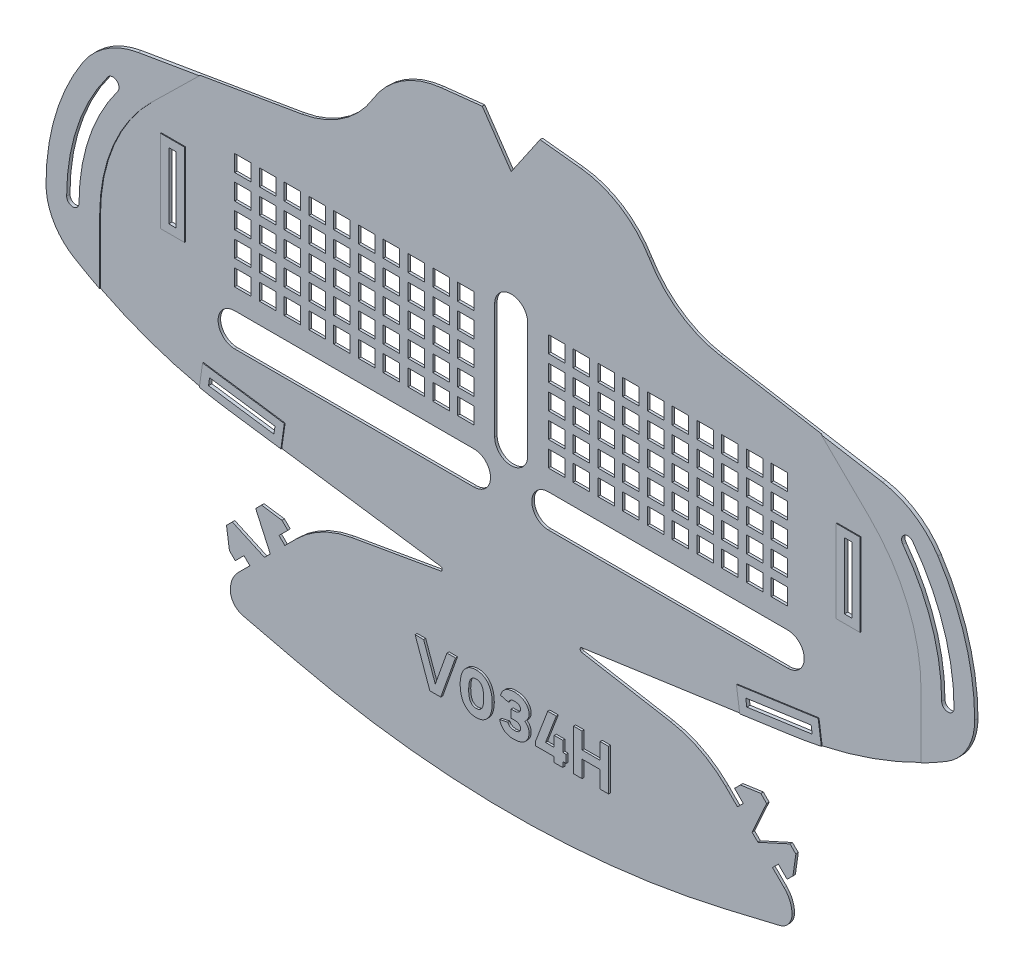
SolidWorks part; units mm, degrees
ref_plane "Front Plane" through (0, 0, 0) normal (0, 0, 1) x (1, 0, 0)
ref_plane "Top Plane" through (0, 0, 0) normal (0, 1, 0) x (1, 0, 0)
ref_plane "Right Plane" through (0, 0, 0) normal (1, 0, 0) x (0, 0, -1)
sketch "Sketch1" plane through (0, 0, 0) normal (0, 0, 1) x (1, 0, 0)
  line L0 (0, 0) -> (0, -145) construction
  line L1 (-14, -102) -> (14, -102) construction
  line L2 (-112.5, -69) -> (112.5, -69) construction
  line L3 (0, -10.2352) -> (-7, 0)
  line L4 (0, -10.2352) -> (7, 0)
  line L5 (7, 0) -> (16.9419, -1.0768)
  line L6 (-90.1804, -30.1909) -> (-50.7439, -23.5)
  line L7 (90.1804, -30.1909) -> (50.7439, -23.5)
  line L8 (-14, -102) -> (-68.2662, -94.2919)
  line L9 (-7, 0) -> (-16.9419, -1.0768)
  line L10 (14, -102) -> (68.2662, -94.2919)
  line L11 (-103.5977, -39) -> (-103.5977, -69) construction
  line L12 (-14, -102) -> (-38.6266, -106.305)
  line L13 (-52, -113.2546) -> (-54.8283, -116.0832)
  line L14 (52, -113.2546) -> (54.8283, -116.0832)
  line L15 (14, -102) -> (38.6266, -106.305)
  line L16 (-54.8283, -116.0832) -> (-56.2426, -114.669)
  line L17 (-56.2426, -114.669) -> (-54.1214, -112.5476)
  line L18 (-54.1214, -112.5476) -> (-55.5356, -111.1334)
  line L19 (-55.5356, -111.1334) -> (-60.4854, -110.4265)
  line L20 (-60.4854, -110.4265) -> (-68.9703, -118.9122)
  line L21 (-64.7275, -123.1546) -> (-63.3132, -124.5688)
  line L22 (-63.3132, -124.5688) -> (-66.1415, -127.3973)
  line L23 (-64.7275, -123.1546) -> (-66.8487, -125.2761)
  line L24 (-66.8487, -125.2761) -> (-68.263, -123.8619)
  line L25 (-68.9703, -118.9122) -> (-68.263, -123.8619)
  line L26 (68.9703, -118.9122) -> (68.263, -123.8619)
  line L27 (66.8487, -125.2761) -> (68.263, -123.8619)
  line L28 (64.7275, -123.1546) -> (66.8487, -125.2761)
  line L29 (63.3132, -124.5688) -> (66.1415, -127.3973)
  line L30 (64.7275, -123.1546) -> (63.3132, -124.5688)
  line L31 (60.4854, -110.4265) -> (68.9703, -118.9122)
  line L32 (55.5356, -111.1334) -> (60.4854, -110.4265)
  line L33 (54.1214, -112.5476) -> (55.5356, -111.1334)
  line L34 (56.2426, -114.669) -> (54.1214, -112.5476)
  line L35 (54.8283, -116.0832) -> (56.2426, -114.669)
  line L36 (-64.9691, -135.8852) -> (-52.4361, -138.8607)
  line L37 (64.9691, -135.8852) -> (52.4361, -138.8607)
  line L38 (-68.9703, -118.9122) -> (-64.7275, -123.1546) construction
  line L39 (-60.4854, -110.4265) -> (-56.2426, -114.669) construction
  arc A0 (-16.9419, -1.0768) -> (-33.4614, -11.6696) centre (-14.5729, -22.9489) ccw
  arc A1 (-33.4614, -11.6696) -> (-50.7439, -23.5) centre (-54.9257, 1.1478) cw
  arc A2 (-103.5977, -39) -> (-90.1804, -30.1909) centre (-86.8349, -49.9091) cw
  arc A3 (-112.5, -69) -> (-103.5977, -39) centre (-57.5, -69) cw
  arc A4 (112.5, -69) -> (103.5977, -39) centre (57.5, -69) ccw
  arc A5 (103.5977, -39) -> (90.1804, -30.1909) centre (86.8349, -49.9091) ccw
  arc A6 (16.9419, -1.0768) -> (33.4614, -11.6696) centre (14.5729, -22.9489) cw
  arc A7 (33.4614, -11.6696) -> (50.7439, -23.5) centre (54.9257, 1.1478) ccw
  arc A8 (-112.5, -69) -> (-105.7111, -81) centre (-98.5, -69) ccw
  arc A9 (-105.7111, -81) -> (-68.2662, -94.2919) centre (-54.2032, 4.7143) ccw
  arc A10 (112.5, -69) -> (105.7111, -81) centre (98.5, -69) cw
  arc A11 (105.7111, -81) -> (68.2662, -94.2919) centre (54.2032, 4.7143) cw
  arc A12 (-38.6266, -106.305) -> (-52, -113.2546) centre (-34.3216, -130.9315) ccw
  arc A13 (38.6266, -106.305) -> (52, -113.2546) centre (34.3216, -130.9315) cw
  arc A14 (-66.1415, -127.3973) -> (-68.0451, -131.9933) centre (-61.5451, -131.9933) ccw
  arc A15 (-68.0451, -131.9933) -> (-64.9691, -135.8852) centre (-64.0451, -131.9933) ccw
  arc A16 (68.0451, -131.9933) -> (64.9691, -135.8852) centre (64.0451, -131.9933) cw
  arc A17 (66.1415, -127.3973) -> (68.0451, -131.9933) centre (61.5451, -131.9933) cw
  arc A19 (-52.4361, -138.8607) -> (0, -145) centre (0, 82) ccw
  arc A20 (52.4361, -138.8607) -> (0, -145) centre (0, 82) cw
  point P8 (0, -102)
  point P11 (0, -69)
  dimension "D5" = 55
  dimension "D11" = 20
  dimension "D13" = 25
  dimension "D16" = 14
  dimension "D15" = 22
  dimension "D18" = 100
  dimension "D22" = 25
  dimension "D31" = 6.5
  dimension "D32" = 4
  dimension "D34" = 227
  dimension "D1" = 145
  dimension "D2" = 28
  dimension "D3" = 43
  dimension "D4" = 76
  dimension "D6" = 225
  dimension "D7" = 14
  dimension "D8" = 12.4
  dimension "D9" = 10
  dimension "D10" = 30
  dimension "D12" = 40
  dimension "D14" = 45.5
  dimension "D17" = 12
  dimension "D19" = 18
  dimension "D20" = 25
  dimension "D21" = 4
  dimension "D23" = 38
  dimension "D24" = 2
  dimension "D25" = 3
  dimension "D26" = 2
  dimension "D27" = 18
  dimension "D29" = 8
  dimension "D30" = 4
extrude "Main Shape" add sketch "Sketch1" along normal blind 0.6
sketch "Sketch2" plane through (0, 0, 0.6) normal (0, 0, 1) x (1, 0, 0)
  line L0 (0, -55) -> (0, 55) construction
  arc A0 (-96.3, -39.9) -> (-106, -69) centre (-57.5, -69) ccw construction
  arc A1 (-97.5, -39) -> (-107.5, -69) centre (-57.5, -69) ccw
  arc A2 (-95.1, -40.8) -> (-104.5, -69) centre (-57.5, -69) ccw
  arc A3 (-95.1, -40.8) -> (-97.5, -39) centre (-96.3, -39.9) ccw
  arc A4 (-107.5, -69) -> (-104.5, -69) centre (-106, -69) ccw
  arc A6 (-103.5977, -39) -> (-112.5, -69) centre (-57.5, -69) ccw construction
  arc A7 (96.3, -39.9) -> (106, -69) centre (57.5, -69) cw construction
  arc A8 (97.5, -39) -> (107.5, -69) centre (57.5, -69) cw
  arc A9 (95.1, -40.8) -> (104.5, -69) centre (57.5, -69) cw
  arc A10 (95.1, -40.8) -> (97.5, -39) centre (96.3, -39.9) cw
  arc A11 (107.5, -69) -> (104.5, -69) centre (106, -69) cw
  point P3 (-103.5111, -53.663)
  point P19 (103.5111, -53.663)
  dimension "D1" = 5
  dimension "D2" = 1.5
extrude "Elastic Attachment Points" cut sketch "Sketch2" against normal through all
sketch "Sketch7" plane through (0, 0, 0.6) normal (0, 0, 1) x (1, 0, 0)
  line L0 (-99.5, -69) -> (-99.5, -84.4384)
  line L1 (-86.8939, -39) -> (-75.3319, -27.6717)
  line L2 (-50.7439, -23.5) -> (-90.1804, -30.1909) construction
  line L3 (-75.3319, -27.6717) -> (-90.1804, -30.1909)
  line L4 (0, -55) -> (0, 55) construction
  line L5 (75.3319, -27.6717) -> (90.1804, -30.1909)
  line L6 (86.8939, -39) -> (75.3319, -27.6717)
  line L7 (99.5, -69) -> (99.5, -84.4384)
  arc A0 (-99.5, -69) -> (-86.8939, -39) centre (-57.5, -69) cw
  arc A1 (-95.1, -40.8) -> (-104.5, -69) centre (-57.5, -69) ccw construction
  arc A2 (-105.7111, -81) -> (-68.2662, -94.2919) centre (-54.2032, 4.7143) ccw construction
  arc A3 (-112.5, -69) -> (-105.7111, -81) centre (-98.5, -69) ccw construction
  arc A4 (-103.5977, -39) -> (-112.5, -69) centre (-57.5, -69) ccw construction
  arc A5 (-90.1804, -30.1909) -> (-103.5977, -39) centre (-86.8349, -49.9091) ccw construction
  arc A6 (-105.7111, -81) -> (-99.5, -84.4384) centre (-54.2032, 4.7143) ccw
  arc A7 (-112.5, -69) -> (-105.7111, -81) centre (-98.5, -69) ccw
  arc A8 (-103.5977, -39) -> (-112.5, -69) centre (-57.5, -69) ccw
  arc A9 (-90.1804, -30.1909) -> (-103.5977, -39) centre (-86.8349, -49.9091) ccw
  arc A10 (90.1804, -30.1909) -> (103.5977, -39) centre (86.8349, -49.9091) cw
  arc A11 (103.5977, -39) -> (112.5, -69) centre (57.5, -69) cw
  arc A12 (112.5, -69) -> (105.7111, -81) centre (98.5, -69) cw
  arc A13 (105.7111, -81) -> (99.5, -84.4384) centre (54.2032, 4.7143) cw
  arc A14 (99.5, -69) -> (86.8939, -39) centre (57.5, -69) ccw
  arc A15 (-107.5, -69) -> (-104.5, -69) centre (-106, -69) ccw construction
  arc A16 (-95.1, -40.8) -> (-97.5, -39) centre (-96.3, -39.9) ccw construction
  arc A17 (-97.5, -39) -> (-107.5, -69) centre (-57.5, -69) ccw construction
  arc A18 (-107.5, -69) -> (-104.5, -69) centre (-106, -69) ccw
  arc A19 (-95.1, -40.8) -> (-97.5, -39) centre (-96.3, -39.9) ccw
  arc A20 (-95.1, -40.8) -> (-104.5, -69) centre (-57.5, -69) ccw
  arc A21 (-97.5, -39) -> (-107.5, -69) centre (-57.5, -69) ccw
  arc A22 (104.5, -69) -> (107.5, -69) centre (106, -69) ccw construction
  arc A23 (97.5, -39) -> (95.1, -40.8) centre (96.3, -39.9) ccw construction
  arc A24 (104.5, -69) -> (95.1, -40.8) centre (57.5, -69) ccw construction
  arc A25 (107.5, -69) -> (97.5, -39) centre (57.5, -69) ccw construction
  arc A26 (104.5, -69) -> (107.5, -69) centre (106, -69) ccw
  arc A27 (97.5, -39) -> (95.1, -40.8) centre (96.3, -39.9) ccw
  arc A28 (104.5, -69) -> (95.1, -40.8) centre (57.5, -69) ccw
  arc A29 (107.5, -69) -> (97.5, -39) centre (57.5, -69) ccw
  dimension "D1" = 5
extrude "Reinforced Attachment Points" add sketch "Sketch7" along normal blind 0.2
sketch "Sketch6" plane through (0, 0, 0.6) normal (0, 0, 1) x (1, 0, 0)
  line L0 (-73.1225, -91.5821) -> (-57.2815, -93.8322)
  line L1 (-57.2815, -93.8322) -> (-57.0283, -92.05)
  line L2 (-57.0283, -92.05) -> (-72.8693, -89.8)
  line L3 (-72.8693, -89.8) -> (-73.1225, -91.5821)
  line L4 (-68.2662, -94.2919) -> (-14, -102) construction
  line L5 (-64.9488, -90.925) -> (-65.202, -92.7071) construction
  line L13 (0, -0.44) -> (0, 0.44) construction
  line L14 (64.9488, -90.925) -> (65.202, -92.7071) construction
  line L15 (73.1225, -91.5821) -> (72.8693, -89.8)
  line L16 (57.0283, -92.05) -> (57.2815, -93.8322)
  line L22 (57.0283, -92.05) -> (72.8693, -89.8)
  line L24 (73.1225, -91.5821) -> (57.2815, -93.8322)
  dimension "D1" = 2
  dimension "D2" = 16
  dimension "D3" = 52
  dimension "D4" = 1.8
extrude "Tab Slits" cut sketch "Sketch6" against normal through all
sketch "Sketch9" plane through (0, 0, 0.6) normal (0, 0, 1) x (1, 0, 0)
  line L4 (-57.2815, -93.8322) -> (-57.0283, -92.05) construction
  line L5 (-73.1225, -91.5821) -> (-57.2815, -93.8322) construction
  line L6 (-72.8693, -89.8) -> (-73.1225, -91.5821) construction
  line L7 (-57.0283, -92.05) -> (-72.8693, -89.8) construction
  line L12 (-57.2815, -93.8322) -> (-57.0283, -92.05)
  line L13 (-73.1225, -91.5821) -> (-57.2815, -93.8322)
  line L14 (-72.8693, -89.8) -> (-73.1225, -91.5821)
  line L15 (-57.0283, -92.05) -> (-72.8693, -89.8)
  line L16 (-55.5826, -96.0935) -> (-54.767, -90.3512)
  line L17 (-68.2662, -94.2919) -> (-14, -102) construction
  line L18 (-54.767, -90.3512) -> (-74.5682, -87.5386)
  line L19 (-74.5682, -87.5386) -> (-75.3475, -93.0248)
  line L20 (-68.2662, -94.2919) -> (-55.5826, -96.0935)
  line L21 (0, -0.44) -> (0, 0.44) construction
  line L22 (68.2662, -94.2919) -> (55.5826, -96.0935)
  line L23 (74.5682, -87.5386) -> (75.3475, -93.0248)
  line L24 (54.767, -90.3512) -> (74.5682, -87.5386)
  line L25 (55.5826, -96.0935) -> (54.767, -90.3512)
  line L26 (57.0283, -92.05) -> (72.8693, -89.8)
  line L27 (72.8693, -89.8) -> (73.1225, -91.5821)
  line L28 (73.1225, -91.5821) -> (57.2815, -93.8322)
  line L29 (57.2815, -93.8322) -> (57.0283, -92.05)
  arc A0 (-99.5, -84.4384) -> (-68.2662, -94.2919) centre (-54.2032, 4.7143) ccw construction
  arc A1 (-75.3475, -93.0248) -> (-68.2662, -94.2919) centre (-54.2032, 4.7143) ccw
  arc A2 (75.3475, -93.0248) -> (68.2662, -94.2919) centre (54.2032, 4.7143) cw
  dimension "D1" = 2
  dimension "D2" = 2
  dimension "D3" = 2
extrude "Reinforced Tab Slits" add sketch "Sketch9" along normal blind 0.2
sketch "Sketch11" plane through (0, 0, 0.6) normal (0, 0, 1) x (1, 0, 0)
  line L0 (-67.5562, -117.4979) -> (-59.7778, -121.0331)
  line L1 (-60.4854, -110.4265) -> (-68.9703, -118.9122) construction
  line L2 (-59.7778, -121.0331) -> (-58.3637, -119.6188)
  line L3 (-58.3637, -119.6188) -> (-61.8996, -111.8408)
  line L4 (-61.8996, -111.8408) -> (-67.5562, -117.4979)
  line L6 (-58.3637, -119.6188) -> (-54.8283, -116.0832) construction
  line L7 (-59.7778, -121.0331) -> (-63.3132, -124.5688) construction
  line L10 (0, -0.44) -> (0, 0.44) construction
  line L11 (59.7778, -121.0331) -> (63.3132, -124.5688) construction
  line L12 (58.3637, -119.6188) -> (54.8283, -116.0832) construction
  line L13 (61.8996, -111.8408) -> (67.5562, -117.4979)
  line L14 (58.3637, -119.6188) -> (61.8996, -111.8408)
  line L15 (59.7778, -121.0331) -> (58.3637, -119.6188)
  line L16 (67.5562, -117.4979) -> (59.7778, -121.0331)
  dimension "D1" = 2
  dimension "D2" = 2
  dimension "D3" = 5
extrude "Tab Flex Relief" cut sketch "Sketch11" against normal through all both and the other way through all
sketch "Sketch3" plane through (0, 0, 0.6) normal (0, 0, 1) x (1, 0, 0)
  line L3 (0, -10.2352) -> (0, -145) construction
  line L4 (-106, -69) -> (-96.3, -69) construction
  line L5 (-96.3, -69) -> (-96.3, -39.9) construction
  line L6 (-13, -39.9) -> (-9, -39.9)
  line L9 (-13, -39.9) -> (-13, -43.9)
  line L12 (-13, -43.9) -> (-9, -43.9)
  line L15 (-9, -39.9) -> (-9, -43.9)
  line L427 (0, -39.9) -> (0, -67.9) construction
  line L428 (4, -39.9) -> (4, -67.9)
  line L429 (-4, -39.9) -> (-4, -67.9)
  line L430 (-19, -39.9) -> (-15, -39.9)
  line L431 (-19, -39.9) -> (-19, -43.9)
  line L432 (-19, -43.9) -> (-15, -43.9)
  line L433 (-15, -39.9) -> (-15, -43.9)
  line L434 (-25, -39.9) -> (-21, -39.9)
  line L435 (-25, -39.9) -> (-25, -43.9)
  line L436 (-25, -43.9) -> (-21, -43.9)
  line L437 (-21, -39.9) -> (-21, -43.9)
  line L438 (-31, -39.9) -> (-27, -39.9)
  line L439 (-31, -39.9) -> (-31, -43.9)
  line L440 (-31, -43.9) -> (-27, -43.9)
  line L441 (-27, -39.9) -> (-27, -43.9)
  line L442 (-37, -39.9) -> (-33, -39.9)
  line L443 (-37, -39.9) -> (-37, -43.9)
  line L444 (-67, -76.9) -> (-9, -76.9) construction
  line L445 (-67, -72.9) -> (-9, -72.9)
  line L446 (-67, -80.9) -> (-9, -80.9)
  line L447 (67, -76.9) -> (9, -76.9) construction
  line L448 (67, -72.9) -> (9, -72.9)
  line L449 (67, -80.9) -> (9, -80.9)
  line L452 (-37, -43.9) -> (-33, -43.9)
  line L453 (-33, -39.9) -> (-33, -43.9)
  line L454 (-43, -39.9) -> (-39, -39.9)
  line L457 (-43, -39.9) -> (-43, -43.9)
  line L458 (-43, -43.9) -> (-39, -43.9)
  line L459 (-39, -39.9) -> (-39, -43.9)
  line L460 (-49, -39.9) -> (-45, -39.9)
  line L461 (-49, -39.9) -> (-49, -43.9)
  line L462 (-49, -43.9) -> (-45, -43.9)
  line L463 (-45, -39.9) -> (-45, -43.9)
  line L464 (-55, -39.9) -> (-51, -39.9)
  line L465 (-55, -39.9) -> (-55, -43.9)
  line L466 (-55, -43.9) -> (-51, -43.9)
  line L467 (-51, -39.9) -> (-51, -43.9)
  line L468 (-61, -39.9) -> (-57, -39.9)
  line L469 (-61, -39.9) -> (-61, -43.9)
  line L470 (-61, -43.9) -> (-57, -43.9)
  line L471 (-57, -39.9) -> (-57, -43.9)
  line L472 (-67, -39.9) -> (-63, -39.9)
  line L473 (-67, -39.9) -> (-67, -43.9)
  line L474 (-67, -43.9) -> (-63, -43.9)
  line L475 (-63, -39.9) -> (-63, -43.9)
  line L476 (-19, -45.9) -> (-15, -45.9)
  line L477 (-19, -45.9) -> (-19, -49.9)
  line L478 (-19, -49.9) -> (-15, -49.9)
  line L479 (-15, -45.9) -> (-15, -49.9)
  line L480 (-25, -45.9) -> (-21, -45.9)
  line L481 (-25, -45.9) -> (-25, -49.9)
  line L482 (-25, -49.9) -> (-21, -49.9)
  line L483 (-21, -45.9) -> (-21, -49.9)
  line L484 (-31, -45.9) -> (-27, -45.9)
  line L485 (-31, -45.9) -> (-31, -49.9)
  line L486 (-31, -49.9) -> (-27, -49.9)
  line L487 (-27, -45.9) -> (-27, -49.9)
  line L488 (-37, -45.9) -> (-33, -45.9)
  line L489 (-37, -45.9) -> (-37, -49.9)
  line L490 (-37, -49.9) -> (-33, -49.9)
  line L491 (-33, -45.9) -> (-33, -49.9)
  line L492 (-43, -45.9) -> (-39, -45.9)
  line L493 (-43, -45.9) -> (-43, -49.9)
  line L494 (-43, -49.9) -> (-39, -49.9)
  line L495 (-39, -45.9) -> (-39, -49.9)
  line L496 (-49, -45.9) -> (-45, -45.9)
  line L497 (-49, -45.9) -> (-49, -49.9)
  line L498 (-49, -49.9) -> (-45, -49.9)
  line L499 (-45, -45.9) -> (-45, -49.9)
  line L500 (-55, -45.9) -> (-51, -45.9)
  line L501 (-55, -45.9) -> (-55, -49.9)
  line L502 (-55, -49.9) -> (-51, -49.9)
  line L503 (-51, -45.9) -> (-51, -49.9)
  line L504 (-61, -45.9) -> (-57, -45.9)
  line L505 (-61, -45.9) -> (-61, -49.9)
  line L506 (-61, -49.9) -> (-57, -49.9)
  line L507 (-57, -45.9) -> (-57, -49.9)
  line L508 (-67, -45.9) -> (-63, -45.9)
  line L509 (-67, -45.9) -> (-67, -49.9)
  line L510 (-67, -49.9) -> (-63, -49.9)
  line L511 (-63, -45.9) -> (-63, -49.9)
  line L512 (-19, -51.9) -> (-15, -51.9)
  line L513 (-19, -51.9) -> (-19, -55.9)
  line L514 (-19, -55.9) -> (-15, -55.9)
  line L515 (-15, -51.9) -> (-15, -55.9)
  line L516 (-25, -51.9) -> (-21, -51.9)
  line L517 (-25, -51.9) -> (-25, -55.9)
  line L518 (-25, -55.9) -> (-21, -55.9)
  line L519 (-21, -51.9) -> (-21, -55.9)
  line L520 (-31, -51.9) -> (-27, -51.9)
  line L521 (-31, -51.9) -> (-31, -55.9)
  line L522 (-31, -55.9) -> (-27, -55.9)
  line L523 (-27, -51.9) -> (-27, -55.9)
  line L524 (-37, -51.9) -> (-33, -51.9)
  line L525 (-37, -51.9) -> (-37, -55.9)
  line L526 (-37, -55.9) -> (-33, -55.9)
  line L527 (-33, -51.9) -> (-33, -55.9)
  line L528 (-43, -51.9) -> (-39, -51.9)
  line L529 (-43, -51.9) -> (-43, -55.9)
  line L530 (-43, -55.9) -> (-39, -55.9)
  line L531 (-39, -51.9) -> (-39, -55.9)
  line L532 (-49, -51.9) -> (-45, -51.9)
  line L533 (-49, -51.9) -> (-49, -55.9)
  line L534 (-49, -55.9) -> (-45, -55.9)
  line L535 (-45, -51.9) -> (-45, -55.9)
  line L536 (-55, -51.9) -> (-51, -51.9)
  line L537 (-55, -51.9) -> (-55, -55.9)
  line L538 (-55, -55.9) -> (-51, -55.9)
  line L539 (-51, -51.9) -> (-51, -55.9)
  line L540 (-61, -51.9) -> (-57, -51.9)
  line L541 (-61, -51.9) -> (-61, -55.9)
  line L542 (-61, -55.9) -> (-57, -55.9)
  line L543 (-57, -51.9) -> (-57, -55.9)
  line L544 (-67, -51.9) -> (-63, -51.9)
  line L545 (-67, -51.9) -> (-67, -55.9)
  line L546 (-67, -55.9) -> (-63, -55.9)
  line L547 (-63, -51.9) -> (-63, -55.9)
  line L548 (-19, -57.9) -> (-15, -57.9)
  line L549 (-19, -57.9) -> (-19, -61.9)
  line L550 (-19, -61.9) -> (-15, -61.9)
  line L551 (-15, -57.9) -> (-15, -61.9)
  line L552 (-25, -57.9) -> (-21, -57.9)
  line L553 (-25, -57.9) -> (-25, -61.9)
  line L554 (-25, -61.9) -> (-21, -61.9)
  line L555 (-21, -57.9) -> (-21, -61.9)
  line L556 (-31, -57.9) -> (-27, -57.9)
  line L557 (-31, -57.9) -> (-31, -61.9)
  line L558 (-31, -61.9) -> (-27, -61.9)
  line L559 (-27, -57.9) -> (-27, -61.9)
  line L560 (-37, -57.9) -> (-33, -57.9)
  line L561 (-37, -57.9) -> (-37, -61.9)
  line L562 (-37, -61.9) -> (-33, -61.9)
  line L563 (-33, -57.9) -> (-33, -61.9)
  line L564 (-43, -57.9) -> (-39, -57.9)
  line L565 (-43, -57.9) -> (-43, -61.9)
  line L566 (-43, -61.9) -> (-39, -61.9)
  line L567 (-39, -57.9) -> (-39, -61.9)
  line L568 (-49, -57.9) -> (-45, -57.9)
  line L569 (-49, -57.9) -> (-49, -61.9)
  line L570 (-49, -61.9) -> (-45, -61.9)
  line L571 (-45, -57.9) -> (-45, -61.9)
  line L572 (-55, -57.9) -> (-51, -57.9)
  line L573 (-55, -57.9) -> (-55, -61.9)
  line L574 (-55, -61.9) -> (-51, -61.9)
  line L575 (-51, -57.9) -> (-51, -61.9)
  line L576 (-61, -57.9) -> (-57, -57.9)
  line L577 (-61, -57.9) -> (-61, -61.9)
  line L578 (-61, -61.9) -> (-57, -61.9)
  line L579 (-57, -57.9) -> (-57, -61.9)
  line L580 (-67, -57.9) -> (-63, -57.9)
  line L581 (-67, -57.9) -> (-67, -61.9)
  line L582 (-67, -61.9) -> (-63, -61.9)
  line L583 (-63, -57.9) -> (-63, -61.9)
  line L584 (-19, -63.9) -> (-15, -63.9)
  line L585 (-19, -63.9) -> (-19, -67.9)
  line L586 (-19, -67.9) -> (-15, -67.9)
  line L587 (-15, -63.9) -> (-15, -67.9)
  line L588 (-25, -63.9) -> (-21, -63.9)
  line L589 (-25, -63.9) -> (-25, -67.9)
  line L590 (-25, -67.9) -> (-21, -67.9)
  line L591 (-21, -63.9) -> (-21, -67.9)
  line L592 (-31, -63.9) -> (-27, -63.9)
  line L593 (-31, -63.9) -> (-31, -67.9)
  line L594 (-31, -67.9) -> (-27, -67.9)
  line L595 (-27, -63.9) -> (-27, -67.9)
  line L596 (-37, -63.9) -> (-33, -63.9)
  line L597 (-37, -63.9) -> (-37, -67.9)
  line L598 (-37, -67.9) -> (-33, -67.9)
  line L599 (-33, -63.9) -> (-33, -67.9)
  line L600 (-43, -63.9) -> (-39, -63.9)
  line L601 (-43, -63.9) -> (-43, -67.9)
  line L602 (-43, -67.9) -> (-39, -67.9)
  line L603 (-39, -63.9) -> (-39, -67.9)
  line L604 (-49, -63.9) -> (-45, -63.9)
  line L605 (-49, -63.9) -> (-49, -67.9)
  line L606 (-49, -67.9) -> (-45, -67.9)
  line L607 (-45, -63.9) -> (-45, -67.9)
  line L608 (-55, -63.9) -> (-51, -63.9)
  line L609 (-55, -63.9) -> (-55, -67.9)
  line L610 (-55, -67.9) -> (-51, -67.9)
  line L611 (-51, -63.9) -> (-51, -67.9)
  line L612 (-61, -63.9) -> (-57, -63.9)
  line L613 (-61, -63.9) -> (-61, -67.9)
  line L614 (-61, -67.9) -> (-57, -67.9)
  line L615 (-57, -63.9) -> (-57, -67.9)
  line L616 (-67, -63.9) -> (-63, -63.9)
  line L617 (-67, -63.9) -> (-67, -67.9)
  line L618 (-67, -67.9) -> (-63, -67.9)
  line L619 (-63, -63.9) -> (-63, -67.9)
  line L620 (-13, -45.9) -> (-9, -45.9)
  line L621 (-13, -45.9) -> (-13, -49.9)
  line L622 (-13, -49.9) -> (-9, -49.9)
  line L623 (-9, -45.9) -> (-9, -49.9)
  line L624 (-13, -51.9) -> (-9, -51.9)
  line L625 (-13, -51.9) -> (-13, -55.9)
  line L626 (-13, -55.9) -> (-9, -55.9)
  line L627 (-9, -51.9) -> (-9, -55.9)
  line L628 (-13, -57.9) -> (-9, -57.9)
  line L629 (-13, -57.9) -> (-13, -61.9)
  line L630 (-13, -61.9) -> (-9, -61.9)
  line L631 (-9, -57.9) -> (-9, -61.9)
  line L632 (-13, -63.9) -> (-9, -63.9)
  line L633 (-13, -63.9) -> (-13, -67.9)
  line L634 (-13, -67.9) -> (-9, -67.9)
  line L635 (-9, -63.9) -> (-9, -67.9)
  line L636 (9, -63.9) -> (9, -67.9)
  line L637 (13, -67.9) -> (9, -67.9)
  line L638 (13, -63.9) -> (13, -67.9)
  line L639 (13, -63.9) -> (9, -63.9)
  line L640 (9, -57.9) -> (9, -61.9)
  line L641 (13, -61.9) -> (9, -61.9)
  line L642 (13, -57.9) -> (13, -61.9)
  line L643 (13, -57.9) -> (9, -57.9)
  line L644 (9, -51.9) -> (9, -55.9)
  line L645 (13, -55.9) -> (9, -55.9)
  line L646 (13, -51.9) -> (13, -55.9)
  line L647 (13, -51.9) -> (9, -51.9)
  line L648 (9, -45.9) -> (9, -49.9)
  line L649 (13, -49.9) -> (9, -49.9)
  line L650 (13, -45.9) -> (13, -49.9)
  line L651 (13, -45.9) -> (9, -45.9)
  line L652 (63, -63.9) -> (63, -67.9)
  line L653 (67, -67.9) -> (63, -67.9)
  line L654 (67, -63.9) -> (67, -67.9)
  line L655 (67, -63.9) -> (63, -63.9)
  line L656 (57, -63.9) -> (57, -67.9)
  line L657 (61, -67.9) -> (57, -67.9)
  line L658 (61, -63.9) -> (61, -67.9)
  line L659 (61, -63.9) -> (57, -63.9)
  line L660 (51, -63.9) -> (51, -67.9)
  line L661 (55, -67.9) -> (51, -67.9)
  line L662 (55, -63.9) -> (55, -67.9)
  line L663 (55, -63.9) -> (51, -63.9)
  line L664 (45, -63.9) -> (45, -67.9)
  line L665 (49, -67.9) -> (45, -67.9)
  line L666 (49, -63.9) -> (49, -67.9)
  line L667 (49, -63.9) -> (45, -63.9)
  line L668 (39, -63.9) -> (39, -67.9)
  line L669 (43, -67.9) -> (39, -67.9)
  line L670 (43, -63.9) -> (43, -67.9)
  line L671 (43, -63.9) -> (39, -63.9)
  line L672 (33, -63.9) -> (33, -67.9)
  line L673 (37, -67.9) -> (33, -67.9)
  line L674 (37, -63.9) -> (37, -67.9)
  line L675 (37, -63.9) -> (33, -63.9)
  line L676 (27, -63.9) -> (27, -67.9)
  line L677 (31, -67.9) -> (27, -67.9)
  line L678 (31, -63.9) -> (31, -67.9)
  line L679 (31, -63.9) -> (27, -63.9)
  line L680 (21, -63.9) -> (21, -67.9)
  line L681 (25, -67.9) -> (21, -67.9)
  line L682 (25, -63.9) -> (25, -67.9)
  line L683 (25, -63.9) -> (21, -63.9)
  line L684 (15, -63.9) -> (15, -67.9)
  line L685 (19, -67.9) -> (15, -67.9)
  line L686 (19, -63.9) -> (19, -67.9)
  line L687 (19, -63.9) -> (15, -63.9)
  line L688 (63, -57.9) -> (63, -61.9)
  line L689 (67, -61.9) -> (63, -61.9)
  line L690 (67, -57.9) -> (67, -61.9)
  line L691 (67, -57.9) -> (63, -57.9)
  line L692 (57, -57.9) -> (57, -61.9)
  line L693 (61, -61.9) -> (57, -61.9)
  line L694 (61, -57.9) -> (61, -61.9)
  line L695 (61, -57.9) -> (57, -57.9)
  line L696 (51, -57.9) -> (51, -61.9)
  line L697 (55, -61.9) -> (51, -61.9)
  line L698 (55, -57.9) -> (55, -61.9)
  line L699 (55, -57.9) -> (51, -57.9)
  line L700 (45, -57.9) -> (45, -61.9)
  line L701 (49, -61.9) -> (45, -61.9)
  line L702 (49, -57.9) -> (49, -61.9)
  line L703 (49, -57.9) -> (45, -57.9)
  line L704 (39, -57.9) -> (39, -61.9)
  line L705 (43, -61.9) -> (39, -61.9)
  line L706 (43, -57.9) -> (43, -61.9)
  line L707 (43, -57.9) -> (39, -57.9)
  line L708 (33, -57.9) -> (33, -61.9)
  line L709 (37, -61.9) -> (33, -61.9)
  line L710 (37, -57.9) -> (37, -61.9)
  line L711 (37, -57.9) -> (33, -57.9)
  line L712 (27, -57.9) -> (27, -61.9)
  line L713 (31, -61.9) -> (27, -61.9)
  line L714 (31, -57.9) -> (31, -61.9)
  line L715 (31, -57.9) -> (27, -57.9)
  line L716 (21, -57.9) -> (21, -61.9)
  line L717 (25, -61.9) -> (21, -61.9)
  line L718 (25, -57.9) -> (25, -61.9)
  line L719 (25, -57.9) -> (21, -57.9)
  line L720 (15, -57.9) -> (15, -61.9)
  line L721 (19, -61.9) -> (15, -61.9)
  line L722 (19, -57.9) -> (19, -61.9)
  line L723 (19, -57.9) -> (15, -57.9)
  line L724 (63, -51.9) -> (63, -55.9)
  line L725 (67, -55.9) -> (63, -55.9)
  line L726 (67, -51.9) -> (67, -55.9)
  line L727 (67, -51.9) -> (63, -51.9)
  line L728 (57, -51.9) -> (57, -55.9)
  line L729 (61, -55.9) -> (57, -55.9)
  line L730 (61, -51.9) -> (61, -55.9)
  line L731 (61, -51.9) -> (57, -51.9)
  line L732 (51, -51.9) -> (51, -55.9)
  line L733 (55, -55.9) -> (51, -55.9)
  line L734 (55, -51.9) -> (55, -55.9)
  line L735 (55, -51.9) -> (51, -51.9)
  line L736 (45, -51.9) -> (45, -55.9)
  line L737 (49, -55.9) -> (45, -55.9)
  line L738 (49, -51.9) -> (49, -55.9)
  line L739 (49, -51.9) -> (45, -51.9)
  line L740 (39, -51.9) -> (39, -55.9)
  line L741 (43, -55.9) -> (39, -55.9)
  line L742 (43, -51.9) -> (43, -55.9)
  line L743 (43, -51.9) -> (39, -51.9)
  line L744 (33, -51.9) -> (33, -55.9)
  line L745 (37, -55.9) -> (33, -55.9)
  line L746 (37, -51.9) -> (37, -55.9)
  line L747 (37, -51.9) -> (33, -51.9)
  line L748 (27, -51.9) -> (27, -55.9)
  line L749 (31, -55.9) -> (27, -55.9)
  line L750 (31, -51.9) -> (31, -55.9)
  line L751 (31, -51.9) -> (27, -51.9)
  line L752 (21, -51.9) -> (21, -55.9)
  line L753 (25, -55.9) -> (21, -55.9)
  line L754 (25, -51.9) -> (25, -55.9)
  line L755 (25, -51.9) -> (21, -51.9)
  line L756 (15, -51.9) -> (15, -55.9)
  line L757 (19, -55.9) -> (15, -55.9)
  line L758 (19, -51.9) -> (19, -55.9)
  line L759 (19, -51.9) -> (15, -51.9)
  line L760 (63, -45.9) -> (63, -49.9)
  line L761 (67, -49.9) -> (63, -49.9)
  line L762 (67, -45.9) -> (67, -49.9)
  line L763 (67, -45.9) -> (63, -45.9)
  line L764 (57, -45.9) -> (57, -49.9)
  line L765 (61, -49.9) -> (57, -49.9)
  line L766 (61, -45.9) -> (61, -49.9)
  line L767 (61, -45.9) -> (57, -45.9)
  line L768 (51, -45.9) -> (51, -49.9)
  line L769 (55, -49.9) -> (51, -49.9)
  line L770 (55, -45.9) -> (55, -49.9)
  line L771 (55, -45.9) -> (51, -45.9)
  line L772 (45, -45.9) -> (45, -49.9)
  line L773 (49, -49.9) -> (45, -49.9)
  line L774 (49, -45.9) -> (49, -49.9)
  line L775 (49, -45.9) -> (45, -45.9)
  line L776 (39, -45.9) -> (39, -49.9)
  line L777 (43, -49.9) -> (39, -49.9)
  line L778 (43, -45.9) -> (43, -49.9)
  line L779 (43, -45.9) -> (39, -45.9)
  line L780 (33, -45.9) -> (33, -49.9)
  line L781 (37, -49.9) -> (33, -49.9)
  line L782 (37, -45.9) -> (37, -49.9)
  line L783 (37, -45.9) -> (33, -45.9)
  line L784 (27, -45.9) -> (27, -49.9)
  line L785 (31, -49.9) -> (27, -49.9)
  line L786 (31, -45.9) -> (31, -49.9)
  line L787 (31, -45.9) -> (27, -45.9)
  line L788 (21, -45.9) -> (21, -49.9)
  line L789 (25, -49.9) -> (21, -49.9)
  line L790 (25, -45.9) -> (25, -49.9)
  line L791 (25, -45.9) -> (21, -45.9)
  line L792 (15, -45.9) -> (15, -49.9)
  line L793 (19, -49.9) -> (15, -49.9)
  line L794 (19, -45.9) -> (19, -49.9)
  line L795 (19, -45.9) -> (15, -45.9)
  line L796 (63, -39.9) -> (63, -43.9)
  line L797 (67, -43.9) -> (63, -43.9)
  line L798 (67, -39.9) -> (67, -43.9)
  line L799 (67, -39.9) -> (63, -39.9)
  line L800 (57, -39.9) -> (57, -43.9)
  line L801 (61, -43.9) -> (57, -43.9)
  line L802 (61, -39.9) -> (61, -43.9)
  line L803 (61, -39.9) -> (57, -39.9)
  line L804 (51, -39.9) -> (51, -43.9)
  line L805 (55, -43.9) -> (51, -43.9)
  line L806 (55, -39.9) -> (55, -43.9)
  line L807 (55, -39.9) -> (51, -39.9)
  line L808 (45, -39.9) -> (45, -43.9)
  line L809 (49, -43.9) -> (45, -43.9)
  line L810 (49, -39.9) -> (49, -43.9)
  line L811 (49, -39.9) -> (45, -39.9)
  line L812 (39, -39.9) -> (39, -43.9)
  line L813 (43, -43.9) -> (39, -43.9)
  line L814 (43, -39.9) -> (43, -43.9)
  line L815 (43, -39.9) -> (39, -39.9)
  line L816 (33, -39.9) -> (33, -43.9)
  line L817 (37, -43.9) -> (33, -43.9)
  line L818 (37, -39.9) -> (37, -43.9)
  line L819 (37, -39.9) -> (33, -39.9)
  line L820 (27, -39.9) -> (27, -43.9)
  line L821 (31, -43.9) -> (27, -43.9)
  line L822 (31, -39.9) -> (31, -43.9)
  line L823 (31, -39.9) -> (27, -39.9)
  line L824 (21, -39.9) -> (21, -43.9)
  line L825 (25, -43.9) -> (21, -43.9)
  line L826 (25, -39.9) -> (25, -43.9)
  line L827 (25, -39.9) -> (21, -39.9)
  line L828 (15, -39.9) -> (15, -43.9)
  line L829 (19, -43.9) -> (15, -43.9)
  line L830 (19, -39.9) -> (19, -43.9)
  line L831 (19, -39.9) -> (15, -39.9)
  line L832 (9, -39.9) -> (9, -43.9)
  line L833 (13, -43.9) -> (9, -43.9)
  line L834 (13, -39.9) -> (13, -43.9)
  line L835 (13, -39.9) -> (9, -39.9)
  arc A2 (-52.4361, -138.8607) -> (52.4361, -138.8607) centre (0, 82) ccw construction
  arc A21 (4, -39.9) -> (-4, -39.9) centre (0, -39.9) ccw
  arc A22 (-4, -67.9) -> (4, -67.9) centre (0, -67.9) ccw
  arc A23 (-67, -72.9) -> (-67, -80.9) centre (-67, -76.9) ccw
  arc A24 (-9, -80.9) -> (-9, -72.9) centre (-9, -76.9) ccw
  arc A25 (67, -72.9) -> (67, -80.9) centre (67, -76.9) cw
  arc A26 (9, -80.9) -> (9, -72.9) centre (9, -76.9) cw
  point P4 (-38, -76.9)
  point P414 (0, -53.9)
  point P430 (38, -76.9)
  dimension "D2" = 4
  dimension "D3" = 5
  dimension "D4" = 5
  dimension "D5" = 28
  dimension "D7" = 2
  dimension "D9" = 5
  dimension "D10" = 8
  dimension "D8" = 8
  dimension "D6" = 10
extrude "Breathing Slits" cut sketch "Sketch3" against normal through all
sketch "Sketch8" plane through (0, 0, 0.6) normal (0, 0, 1) x (1, 0, 0)
  line L0 (-67.0266, -128.5) -> (67.0266, -128.5) construction
  line L1 (0, -10.2352) -> (0, -145) construction
  arc A0 (-52.4361, -138.8607) -> (52.4361, -138.8607) centre (0, 82) ccw construction
  arc A1 (-66.1415, -127.3973) -> (-68.0451, -131.9933) centre (-61.5451, -131.9933) ccw construction
  text T0 "<b>V034H</b>" font "Double Porter 3" height 10
  point P9 (0, -128.5)
  dimension "D2" = 16.5
extrude "Version Number" add sketch "Sketch8" along normal blind 0.5
fillet "Fillet1" radius 0.5 2 edges at (-14, -102, 0.3) (14, -102, 0.3)
sketch "Sketch12" plane through (0, 0, 0.6) normal (0, 0, 1) x (1, 0, 0)
  line L0 (-106, -69) -> (-96.3, -69) construction
  line L1 (-96.3, -69) -> (-96.3, -39.9) construction
  line L2 (-82.7459, -46.45) -> (-80.9459, -46.45)
  line L3 (-82.7459, -46.45) -> (-82.7459, -62.45)
  line L4 (-82.7459, -62.45) -> (-80.9459, -62.45)
  line L5 (-80.9459, -46.45) -> (-80.9459, -62.45)
  line L6 (0, -10.2352) -> (0, -145) construction
  line L9 (80.9459, -46.45) -> (80.9459, -62.45)
  line L10 (82.7459, -62.45) -> (80.9459, -62.45)
  line L11 (82.7459, -46.45) -> (82.7459, -62.45)
  line L12 (82.7459, -46.45) -> (80.9459, -46.45)
  arc A1 (-52.4361, -138.8607) -> (52.4361, -138.8607) centre (0, 82) ccw construction
  point P9 (-80.9459, -54.45)
  point P13 (-96.3, -54.45)
  dimension "D1" = 16
  dimension "D2" = 1.8
  dimension "D3" = 80.9459
extrude "Tab Overlay Slit" cut sketch "Sketch12" against normal through all both and the other way through all
sketch "Sketch13" plane through (0, 0, 0.6) normal (0, 0, 1) x (1, 0, 0)
  line L0 (-80.9459, -62.45) -> (-82.7459, -62.45) construction
  line L1 (-84.7459, -44.45) -> (-78.9459, -44.45)
  line L2 (-84.7459, -44.45) -> (-84.7459, -64.45)
  line L3 (-84.7459, -64.45) -> (-78.9459, -64.45)
  line L4 (-78.9459, -44.45) -> (-78.9459, -64.45)
  line L5 (-82.7459, -62.45) -> (-82.7459, -46.45) construction
  line L6 (-80.9459, -46.45) -> (-80.9459, -62.45) construction
  line L7 (-82.7459, -46.45) -> (-80.9459, -46.45) construction
  line L8 (-80.9459, -62.45) -> (-82.7459, -62.45)
  line L9 (-80.9459, -46.45) -> (-80.9459, -62.45)
  line L10 (-82.7459, -46.45) -> (-80.9459, -46.45)
  line L11 (-82.7459, -62.45) -> (-82.7459, -46.45)
  line L12 (0, -0.605) -> (0, 0.605) construction
  line L13 (82.7459, -62.45) -> (82.7459, -46.45)
  line L14 (82.7459, -46.45) -> (80.9459, -46.45)
  line L15 (80.9459, -46.45) -> (80.9459, -62.45)
  line L16 (80.9459, -62.45) -> (82.7459, -62.45)
  line L17 (78.9459, -44.45) -> (78.9459, -64.45)
  line L18 (84.7459, -64.45) -> (78.9459, -64.45)
  line L19 (84.7459, -44.45) -> (84.7459, -64.45)
  line L20 (84.7459, -44.45) -> (78.9459, -44.45)
  point P8 (-81.8459, -64.45)
  point P9 (-81.8459, -62.45)
  point P10 (-82.7459, -54.45)
  point P11 (-84.7459, -54.45)
  dimension "D1" = 2
  dimension "D2" = 2
extrude "Tab Overlay Reinforcement" add sketch "Sketch13" along normal blind 0.2
